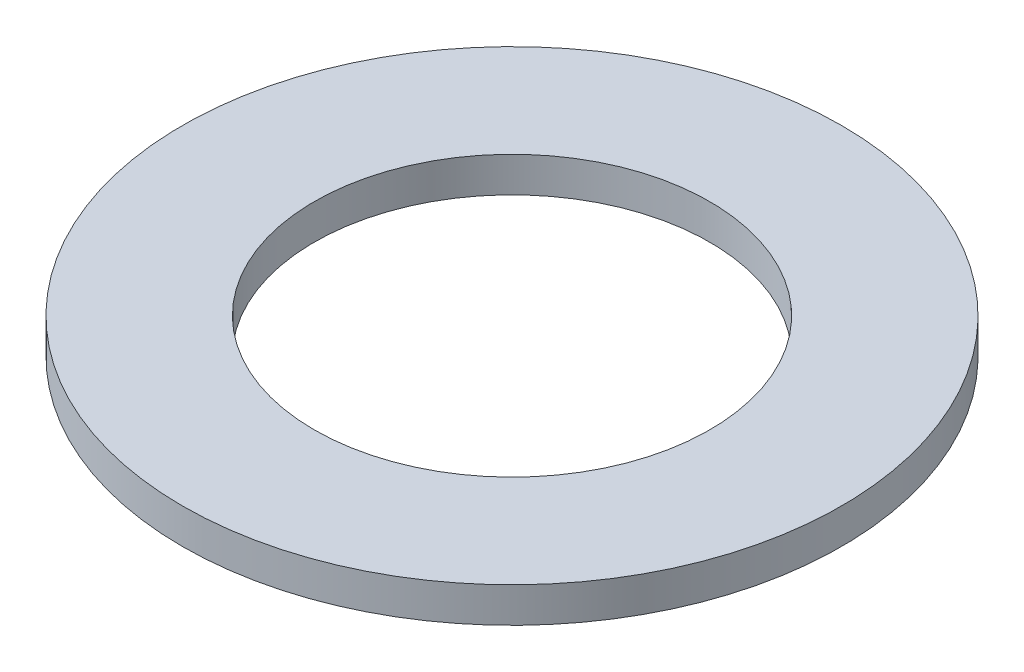
SolidWorks part; units mm, degrees
ref_plane "Front Plane" through (0, 0, 0) normal (0, 0, 1) x (1, 0, 0)
ref_plane "Top Plane" through (0, 0, 0) normal (0, 1, 0) x (1, 0, 0)
ref_plane "Right Plane" through (0, 0, 0) normal (1, 0, 0) x (0, 0, -1)
sketch "Sketch1" plane through (0, 0, 0) normal (0, 1, 0) x (1, 0, 0)
  circle A0 centre (0, 0) radius 75
  dimension "FLANGE_OD" = 150
extrude "Boss-Extrude1" add sketch "Sketch1" along normal blind 8
sketch "Sketch2" plane through (0, 0, 0) normal (0, 1, 0) x (1, 0, 0)
  circle A0 centre (0, 0) radius 45
  dimension "BORE_D" = 90
extrude "Cut-Extrude1" cut sketch "Sketch2" along normal through all
sketch "Sketch3" plane through (0, 8, 0) normal (0, 1, 0) x (1, 0, 0)
  circle A0 centre (0, 0) radius 32.6067 construction
  circle A1 centre (-32.6067, 0) radius 2.0003
  dimension "BOLT_D" = 4.0005
  dimension "BOLT_PCD" = 65.2133
extrude "Cut-Extrude2" cut sketch "Sketch3" against normal blind 6.8879 rebuild error yes
pattern_circular "CirPattern1" count 5 over 360 rebuild error yes
